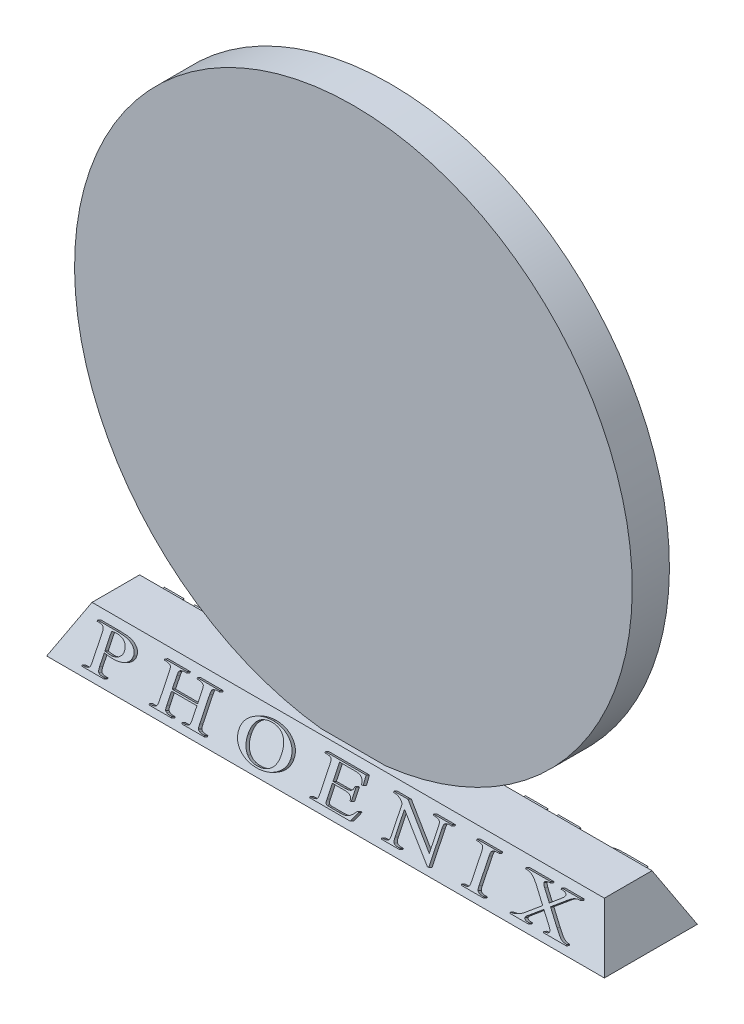
SolidWorks part; units mm, degrees
ref_plane "Front Plane" through (0, 0, 0) normal (0, 0, 1) x (1, 0, 0)
ref_plane "Top Plane" through (0, 0, 0) normal (0, 1, 0) x (1, 0, 0)
ref_plane "Right Plane" through (0, 0, 0) normal (1, 0, 0) x (0, 0, -1)
sketch "Sketch1" plane through (0, 0, 0) normal (0, 1, 0) x (1, 0, 0)
  line L1 (38.1, -6.35) -> (-38.1, -6.35)
  line L2 (38.1, -6.35) -> (38.1, 6.35)
  line L3 (38.1, 6.35) -> (-38.1, 6.35)
  line L4 (-38.1, -6.35) -> (-38.1, 6.35)
  line L5 (38.1, -6.35) -> (-38.1, 6.35) construction
  line L6 (38.1, 6.35) -> (-38.1, -6.35) construction
  point P0 (0, 0)
extrude "Boss-Extrude1" add sketch "Sketch1" along normal blind 6.35 draft 26
sketch "Sketch2" plane through (0, 0, 0) normal (0, 0, 1) x (1, 0, 0)
  circle A0 centre (0, 44.196) radius 38.1
extrude "Boss-Extrude2" add sketch "Sketch2" along normal blind 2.54 and the other way blind 2.54
sketch "Sketch5" plane through (0, 2.5019, 5.1297) normal (0, 0.4384, 0.8988) x (1, 0, 0)
  text T0 "PHOENIX" font "Times New Roman" height in points 20
sketch "Sketch6" plane through (0, 2.5019, -5.1297) normal (0, 0.4384, -0.8988) x (-1, 0, 0)
  text T0 "PHOENIX" font "Times New Roman" height in points 20
extrude "Boss-Extrude3" add sketch "Sketch5" along normal blind 0.508
extrude "Boss-Extrude4" add sketch "Sketch6" along normal blind 0.508
